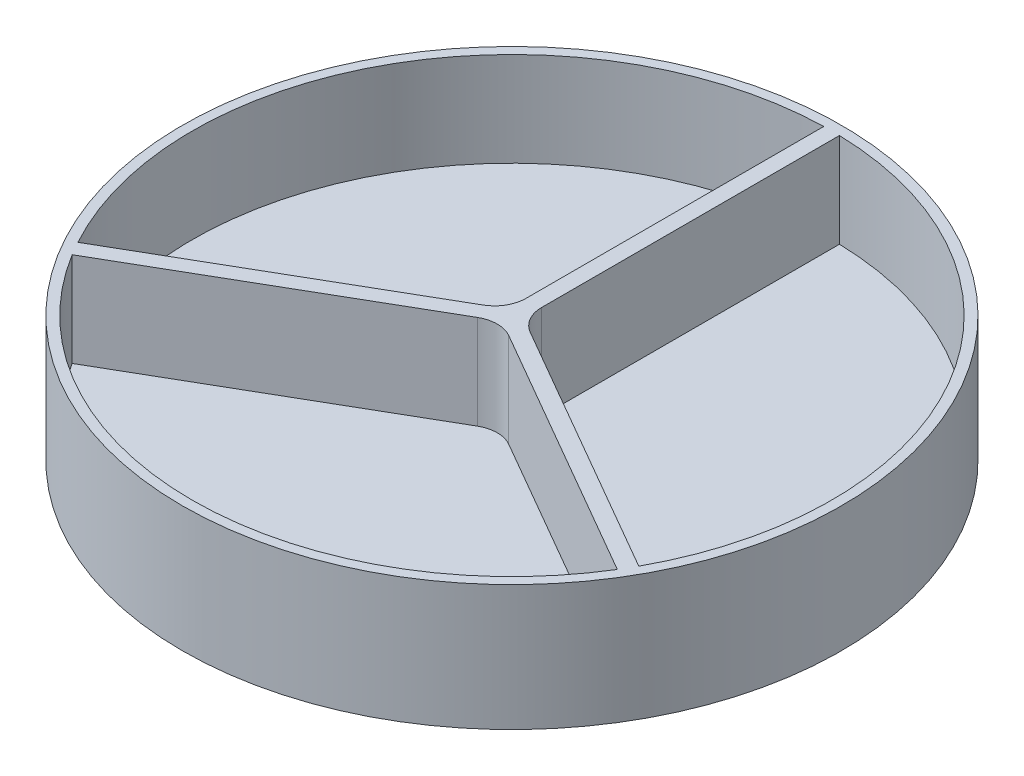
SolidWorks part; units mm, degrees
ref_plane "Front Plane" through (0, 0, 0) normal (0, 0, 1) x (1, 0, 0)
ref_plane "Top Plane" through (0, 0, 0) normal (0, 1, 0) x (1, 0, 0)
ref_plane "Right Plane" through (0, 0, 0) normal (1, 0, 0) x (0, 0, -1)
sketch "Sketch2" plane through (0, 0, 0) normal (0, 1, 0) x (1, 0, 0)
  line L0 (0, 81.5) -> (0, 0) construction
  line L1 (-2, 81.4755) -> (-2, 5.5796)
  line L2 (2, 81.4755) -> (2, 5.5796)
  line L3 (71.4793, -39.1531) -> (6, -1.3486)
  line L4 (69.4721, -42.6131) -> (4, -4.8127)
  line L5 (-69.4721, -42.6131) -> (-4, -4.8127)
  line L6 (-71.4793, -39.1531) -> (-6, -1.3486)
  circle A0 centre (0, 0) radius 81.5
  circle A1 centre (0, 0) radius 84
  arc A2 (-6, -1.3486) -> (-2, 5.5796) centre (-10, 5.5796) ccw
  arc A3 (2, 5.5796) -> (6, -1.3486) centre (10, 5.5796) ccw
  arc A4 (-4, -4.8127) -> (4, -4.8127) centre (0, -11.7409) cw
  point P20 (0, -0.1939)
  dimension "D1" = 163
  dimension "D2" = 168
  dimension "D4" = 8
  dimension "D6" = 8
  dimension "D3" = 3
  dimension "D5" = 4
extrude "Boss-Extrude2" add sketch "Sketch2" along normal blind 8 contours L6 A2 L1 A0 | L2 A3 L3 A0 | A4 L5 A0 L4 region at (-39.9216, 0, -22.9672) region at (39.9216, 0, -22.9672) region at (0, 0, 46.2013)
extrude "Boss-Extrude3" add sketch "Sketch2<4>" along normal blind 32 contours L5 A4 L4 A0 L3 A3 L2 L1 A2 L6 | A1 A0 region at (0, 0, 0.0971) region at (-81.6241, 0, 0)
sketch "Sketch2<4>" plane through (0, 0, 0) normal (0, 1, 0) x (1, 0, 0) same geometry as "Sketch2"
sketch "Sketch3" plane through (0, 0, 0) normal (0, 1, 0) x (1, 0, 0)
sketch "Sketch4" plane through (0, 0, 0) normal (0, 1, 0) x (1, 0, 0)
  circle A0 centre (0, 0) radius 2.95
  dimension "D1" = 5.9
extrude "Cut-Extrude2" cut sketch "Sketch4" along normal blind 8
